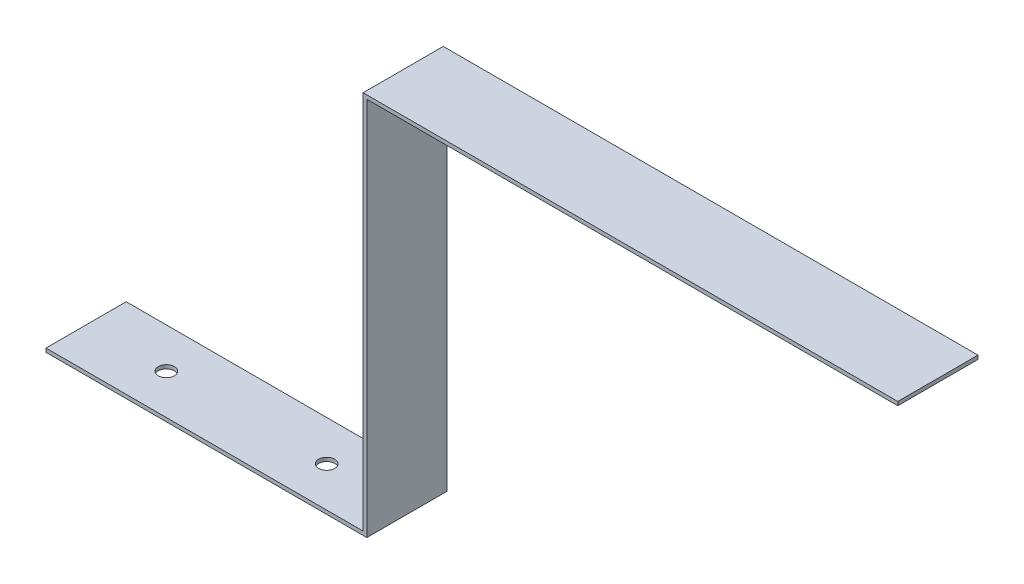
SolidWorks part; units mm, degrees
ref_plane "Front Plane" through (0, 0, 0) normal (0, 0, 1) x (1, 0, 0)
ref_plane "Top Plane" through (0, 0, 0) normal (0, 1, 0) x (1, 0, 0)
ref_plane "Right Plane" through (0, 0, 0) normal (1, 0, 0) x (0, 0, -1)
sketch "Sketch1" plane through (0, 0, 0) normal (0, 0, 1) x (1, 0, 0)
  line L0 (0, 0) -> (60, 0)
  line L1 (60, 0) -> (60, 71)
  line L2 (60, 71) -> (159.3, 71)
  line L3 (159.3, 71) -> (159.3, 71.7)
  line L4 (159.3, 71.7) -> (59.3, 71.7)
  line L5 (59.3, 71.7) -> (59.3, 0.7)
  line L6 (59.3, 0.7) -> (0, 0.7)
  line L7 (0, 0.7) -> (0, 0)
  dimension "D1" = 71
  dimension "D2" = 60
  dimension "D3" = 0.7
  dimension "D4" = 0.7
  dimension "D5" = 0.7
  dimension "D6" = 100
extrude "Boss-Extrude1" add sketch "Sketch1" along normal blind 15
sketch "Sketch2" plane through (0, 0.7, 0) normal (0, 1, 0) x (1, 0, 0)
  line L0 (0, -7.5) -> (59.3, -7.5) construction
  line L1 (0, -15) -> (0, 0) construction
  line L2 (59.3, -15) -> (59.3, 0) construction
  circle A0 centre (15, -7.5) radius 1.5
  circle A1 centre (45, -7.5) radius 1.5
  dimension "D1" = 3
  dimension "D2" = 15
  dimension "D4" = 30
extrude "Cut-Extrude1" cut sketch "Sketch2" against normal through all
